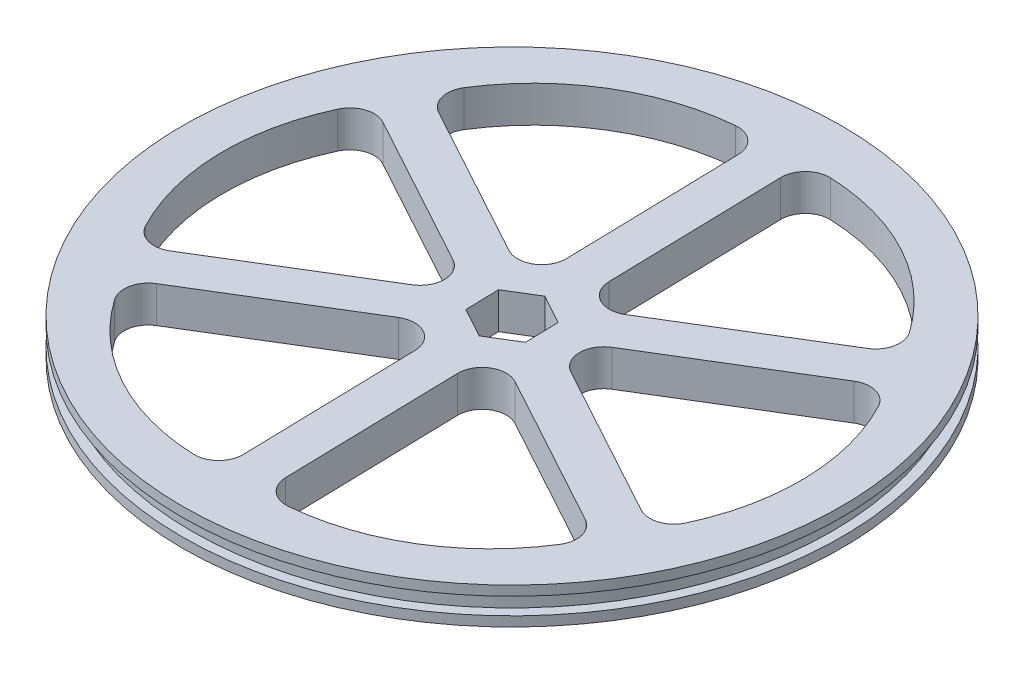
SolidWorks part; units mm, degrees
ref_plane "Front Plane" through (0, 0, 0) normal (0, 0, 1) x (1, 0, 0)
ref_plane "Top Plane" through (0, 0, 0) normal (0, 1, 0) x (1, 0, 0)
ref_plane "Right Plane" through (0, 0, 0) normal (1, 0, 0) x (0, 0, -1)
sketch "Sketch1" plane through (0, 0, 0) normal (0, 1, 0) x (1, 0, 0)
  circle A0 centre (0, 0) radius 68
  circle A1 centre (0, 0) radius 66
extrude "Boss-Extrude1" add sketch "Sketch1" along normal blind 7.5 contours A1
extrude "Boss-Extrude3" add sketch "Sketch1<4>" along normal blind 2
sketch "Sketch1<4>" plane through (0, 0, 0) normal (0, 1, 0) x (1, 0, 0) same geometry as "Sketch1"
sketch "Sketch4" plane through (0, 7.5, 0) normal (0, 1, 0) x (1, 0, 0)
  circle A0 centre (0, 0) radius 68
extrude "Boss-Extrude4" add sketch "Sketch4" against normal blind 2
sketch "Sketch6" plane through (0, 7.5, 0) normal (0, 1, 0) x (1, 0, 0)
  line L1 (-6.0822, 3.3176) -> (-5.9142, -3.6086)
  line L2 (-5.9142, -3.6086) -> (0.168, -6.9262)
  line L3 (0.168, -6.9262) -> (6.0822, -3.3176)
  line L4 (6.0822, -3.3176) -> (5.9142, 3.6086)
  line L5 (5.9142, 3.6086) -> (-0.168, 6.9262)
  line L6 (-0.168, 6.9262) -> (-6.0822, 3.3176)
  circle A0 centre (0, 0) radius 6 construction
extrude "Cut-Extrude1" cut sketch "Sketch6" against normal through all
sketch "Sketch7" plane through (0, 7.5, 0) normal (0, 1, 0) x (1, 0, 0)
  line L2 (-4.4273, 7.256) -> (-48.322, 31.1986)
  line L3 (-4.4273, 7.256) -> (-5.6397, 57.2413)
  arc A0 (-48.322, 31.1986) -> (-5.6397, 57.2413) centre (-6.9599, 11.4068) cw
  dimension "D1" = 60
extrude "Cut-Extrude2" cut sketch "Sketch7" against normal through all contours L3 A0 L2
fillet "Fillet1" radius 5 3 edges at (-4.4273, 3.75, -7.256) (-5.6397, 3.75, -57.2413) (-48.322, 3.75, -31.1986)
sketch "Sketch8" plane through (0, 0, 0) normal (1, 0, 0) x (0, 0, -1)
  line L0 (0, 0) -> (0, 25)
pattern_circular "CirPattern1" count 6 every 60 about axis through (0, 0, 0) along (0, 1, 0) of "Cut-Extrude2", "Fillet1"
